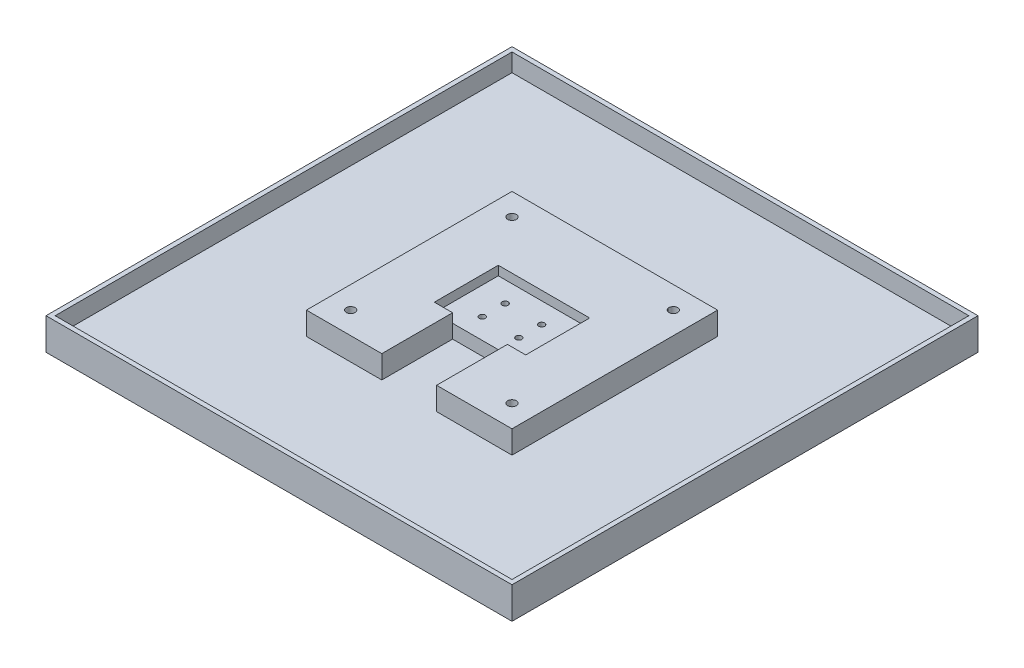
SolidWorks part; units mm, degrees
ref_plane "Front Plane" through (0, 0, 0) normal (0, 0, 1) x (1, 0, 0)
ref_plane "Top Plane" through (0, 0, 0) normal (0, 1, 0) x (1, 0, 0)
ref_plane "Right Plane" through (0, 0, 0) normal (1, 0, 0) x (0, 0, -1)
sketch "Sketch1" plane through (0, 0, 0) normal (0, 1, 0) x (1, 0, 0)
  line L0 (-129.54, 129.54) -> (129.54, 129.54)
  line L1 (-127, -127) -> (127, -127)
  line L2 (-127, -127) -> (-127, 127)
  line L3 (-127, 127) -> (127, 127)
  line L4 (127, -127) -> (127, 127)
  line L5 (-127, -127) -> (127, 127) construction
  line L6 (-127, 127) -> (127, -127) construction
  line L7 (129.54, -129.54) -> (129.54, 129.54)
  line L8 (-129.54, -129.54) -> (129.54, -129.54)
  line L9 (-129.54, -129.54) -> (-129.54, 129.54)
  point P0 (0, 0)
  dimension "D1" = 254
  dimension "D2" = 2.54
extrude "Boss-Extrude1" add sketch "Sketch1" along normal blind 10
extrude "Boss-Extrude2" add sketch "Sketch1<2>" against normal blind 7.62 contours L1 L4 L3 L2 | L9 L8 L7 L0 L4 L1 L2 L3 region at (0, 0, -129.1736) region at (0, 0, 0)
sketch "Sketch1<2>" plane through (0, 0, 0) normal (0, 1, 0) x (1, 0, 0) same geometry as "Sketch1"
sketch "Sketch2" plane through (0, 0, 0) normal (0, 1, 0) x (1, 0, 0)
  line L0 (15.24, -17.78) -> (25.4, -17.78)
  line L1 (-44.845, -44.845) -> (-15.24, -44.845) construction
  line L2 (-44.845, -44.845) -> (-44.845, 44.845) construction
  line L3 (-44.845, 44.845) -> (44.845, 44.845) construction
  line L4 (44.845, -44.845) -> (44.845, 44.845) construction
  line L5 (-44.845, -44.845) -> (44.845, 44.845) construction
  line L6 (-44.845, 44.845) -> (0, 0) construction
  line L7 (-57.15, -57.15) -> (-15.24, -57.15)
  line L8 (-57.15, -57.15) -> (-57.15, 57.15)
  line L9 (-57.15, 57.15) -> (57.15, 57.15)
  line L10 (57.15, -57.15) -> (57.15, 57.15)
  line L11 (-57.15, -57.15) -> (57.15, 57.15) construction
  line L12 (-57.15, 57.15) -> (0, 0) construction
  line L13 (-25.4, -17.78) -> (-15.24, -17.78)
  line L14 (-25.4, -17.78) -> (-25.4, 17.78)
  line L15 (-25.4, 17.78) -> (25.4, 17.78)
  line L16 (25.4, -17.78) -> (25.4, 17.78)
  line L17 (-25.4, -17.78) -> (25.4, 17.78) construction
  line L18 (-25.4, 17.78) -> (0, 0) construction
  line L20 (-15.24, -17.78) -> (-15.24, -57.15)
  line L22 (15.24, -17.78) -> (15.24, -57.15)
  line L23 (17.78, -17.78) -> (57.15, -57.15) construction
  line L24 (17.78, -17.78) -> (44.845, -44.845) construction
  line L25 (15.24, -57.15) -> (57.15, -57.15)
  line L26 (15.24, -44.845) -> (44.845, -44.845) construction
  circle A0 centre (44.845, 44.845) radius 2.413
  circle A1 centre (44.845, -44.845) radius 2.413
  circle A2 centre (-44.845, -44.845) radius 2.413
  circle A3 centre (-44.845, 44.845) radius 2.413
  point P0 (0, 0)
  point P6 (0, 0)
  point P15 (0, 0)
  dimension "D3" = 4.826
  dimension "D4" = 4.826
  dimension "D5" = 4.826
  dimension "D6" = 4.826
  dimension "D1" = 89.69
  dimension "D2" = 114.3
  dimension "D7" = 50.8
  dimension "D8" = 35.56
  dimension "D9" = 10.16
  dimension "D10" = 10.16
extrude "Boss-Extrude3" add sketch "Sketch2" along normal blind 12.7
sketch "Sketch3" plane through (0, 0, 0) normal (0, 1, 0) x (1, 0, 0)
  line L0 (25.4, 17.78) -> (25.4, -17.78) construction
  line L1 (-25.4, 17.78) -> (25.4, 17.78) construction
  line L2 (-25.4, -17.78) -> (-25.4, 17.78) construction
  line L3 (25.4, 17.78) -> (25.4, -17.78) construction
  line L4 (-25.4, 17.78) -> (25.4, 17.78) construction
  line L5 (-25.4, -17.78) -> (-25.4, 17.78) construction
  line L7 (-25.4, 17.78) -> (25.4, 17.78)
  line L8 (-25.4, 17.78) -> (-25.4, -17.78)
  line L9 (-25.4, -17.78) -> (25.4, -17.78)
  line L10 (25.4, 17.78) -> (25.4, -17.78)
  line L11 (-10.16, -6.35) -> (10.16, -6.35) construction
  line L12 (-10.16, -6.35) -> (-10.16, 6.35) construction
  line L13 (-10.16, 6.35) -> (10.16, 6.35) construction
  line L14 (10.16, -6.35) -> (10.16, 6.35) construction
  line L15 (-10.16, -6.35) -> (10.16, 6.35) construction
  line L16 (-10.16, 6.35) -> (10.16, -6.35) construction
  circle A0 centre (10.16, 6.35) radius 1.651
  circle A1 centre (10.16, -6.35) radius 1.651
  circle A2 centre (-10.16, -6.35) radius 1.651
  circle A3 centre (-10.16, 6.35) radius 1.6813
  point P4 (0, 0)
  dimension "D3" = 3.302
  dimension "D4" = 3.302
  dimension "D5" = 3.302
  dimension "D6" = 3.3626
  dimension "D1" = 20.32
  dimension "D2" = 12.7
extrude "Boss-Extrude4" add sketch "Sketch3" along normal blind 7.62
